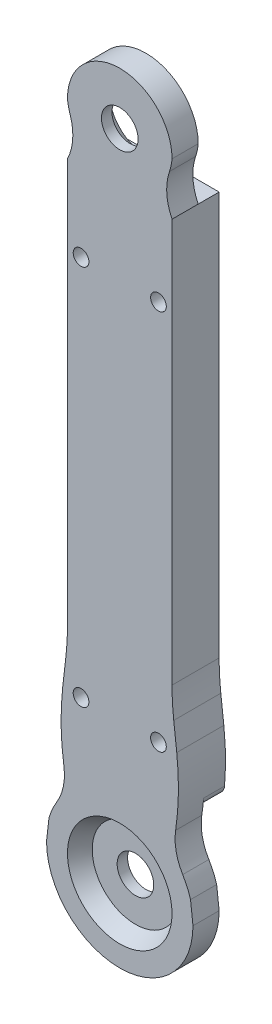
SolidWorks part; units mm, degrees
ref_plane "Front Plane" through (0, 0, 0) normal (0, 0, 1) x (1, 0, 0)
ref_plane "Top Plane" through (0, 0, 0) normal (0, 1, 0) x (1, 0, 0)
ref_plane "Right Plane" through (0, 0, 0) normal (1, 0, 0) x (0, 0, -1)
sketch "Sketch1" plane through (0, 0, 0) normal (0, 0, 1) x (1, 0, 0)
  line L1 (-14, 0) -> (-10, 35)
  line L2 (-10, 35) -> (10, 35)
  line L3 (14, 0) -> (10, 35)
  arc A0 (-14, 0) -> (13.639, 3.1587) centre (0, 0) ccw
  dimension "D1" = 28
  dimension "D3" = 35
extrude "Boss-Extrude1" add sketch "Sketch1" along normal blind 5 contours L1 A0 L3 L2 region at (0, 10.5011, 0)
sketch "Sketch2" plane through (0, 0, 5) normal (0, 0, 1) x (1, 0, 0)
  line L0 (-10, 35) -> (-10, 125) construction
  line L2 (10, 35) -> (-10, 35)
  line L3 (10, 35) -> (10, 125)
  line L4 (10, 125) -> (-10, 125)
  line L5 (-10, 35) -> (-10, 125)
  dimension "D1" = 90
extrude "Boss-Extrude2" add sketch "Sketch2" against normal blind 5
sketch "Sketch3" plane through (0, 0, 0) normal (0, 0, -1) x (-1, 0, 0)
  line L0 (-14, 0) -> (-10, 35) construction
  line L1 (-13.5314, 4.1) -> (-11.7143, 20)
  line L2 (-29.2308, 20) -> (51.5623, 20) construction
  line L3 (-29.2308, 4.1) -> (51.5623, 4.1) construction
  line L4 (-11.7143, 20) -> (-10, 10.0973)
  line L5 (0, 0) -> (0, 31.7524) construction
  line L6 (11.7143, 20) -> (10, 10.0973)
  line L7 (13.5314, 4.1) -> (11.7143, 20)
  arc A0 (-10, 10.0973) -> (-13.5314, 4.1) centre (0.1152, 0.1027) ccw
  arc A1 (10, 10.0973) -> (13.5314, 4.1) centre (-0.1152, 0.1027) cw
  dimension "D4" = 14.22
  dimension "D1" = 4.1
  dimension "D2" = 20
  dimension "D3" = 10.05
  dimension "D5" = 10
extrude "Cut-Extrude1" cut sketch "Sketch3" against normal blind 5
sketch "Sketch4" plane through (0, 0, 0) normal (0, 0, -1) x (-1, 0, 0)
  line L0 (-10.6635, 13.93) -> (10.6635, 13.93) construction
  line L1 (-10, 10.0973) -> (-11.7143, 20) construction
  line L2 (11.7143, 20) -> (10, 10.0973) construction
  line L3 (11.7143, 20) -> (10, 35) construction
  line L4 (-11.7143, 20) -> (-10, 35) construction
  line L5 (10, 125) -> (10, 35) construction
  line L6 (-10, 35) -> (-10, 125) construction
  line L7 (11.7143, 20) -> (10.6635, 13.93)
  line L8 (-10.6635, 13.93) -> (-11.7143, 20)
  line L9 (11.7143, 20) -> (10, 35)
  line L10 (-11.7143, 20) -> (-10, 35)
  line L11 (10, 115) -> (10, 35)
  line L12 (-10, 35) -> (-10, 115)
  line L13 (-10, 115) -> (10, 115)
  line L14 (-10, 125) -> (10, 125) construction
  arc A0 (-10.6635, 13.93) -> (10.6635, 13.93) centre (0, -0.0089) cw
  dimension "D2" = 17.55
  dimension "D1" = 13.93
  dimension "D3" = 10
extrude "Boss-Extrude3" add sketch "Sketch4" along normal blind 4
sketch "Sketch5" plane through (0, 0, 0) normal (0, 0, -1) x (-1, 0, 0)
  circle A0 centre (0, 0) radius 3.5
  dimension "D1" = 7
extrude "Cut-Extrude2" cut sketch "Sketch5" against normal blind 32
sketch "Sketch6" plane through (0, 0, 5) normal (0, 0, 1) x (1, 0, 0)
  circle A0 centre (0, 0) radius 10
  dimension "D1" = 20
extrude "Cut-Extrude3" cut sketch "Sketch6" against normal blind 3 draft 30
sketch "Sketch7" plane through (0, 0, 5) normal (0, 0, 1) x (1, 0, 0)
  line L0 (0, 0) -> (0, 125) construction
  line L1 (10, 125) -> (-10, 125) construction
  line L3 (-7.4, 100) -> (7.4, 100) construction
  line L4 (-7.4, 100) -> (-7.4, 27.09) construction
  line L5 (-7.4, 27.09) -> (7.4, 27.09) construction
  line L6 (7.4, 100) -> (7.4, 27.09) construction
  circle A0 centre (-7.4, 27.09) radius 1.5
  circle A1 centre (7.4, 27.09) radius 1.5
  circle A2 centre (-7.4, 100) radius 1.5
  circle A3 centre (7.4, 100) radius 1.5
  dimension "D4" = 3
  dimension "D5" = 3
  dimension "D6" = 3
  dimension "D7" = 3
  dimension "D1" = 25
  dimension "D2" = 14.8
  dimension "D3" = 72.91
extrude "Cut-Extrude4" cut sketch "Sketch7" against normal through all
sketch "Sketch8" plane through (0, 0, -4) normal (0, 0, -1) x (-1, 0, 0)
  line L0 (0, 115) -> (0, 0) construction
  line L1 (10, 115) -> (-10, 115) construction
  line L2 (3, 115) -> (-3, 115)
  line L3 (-3, 115) -> (-3, 100)
  line L4 (-3, 100) -> (-7, 91.1451)
  line L5 (-7, 91.1451) -> (-7, 41.1451)
  line L6 (-7, 66.1451) -> (10, 66.1451) construction
  line L7 (10, 35) -> (10, 115) construction
  line L8 (-3, 32.2902) -> (-7, 41.1451)
  line L9 (-3, 17.2902) -> (-3, 32.2902)
  line L10 (3, 17.2902) -> (-3, 17.2902)
  line L11 (7, 66.1451) -> (-10, 66.1451) construction
  line L12 (3, 17.2902) -> (3, 32.2902)
  line L13 (3, 32.2902) -> (7, 41.1451)
  line L14 (7, 91.1451) -> (7, 41.1451)
  line L15 (3, 100) -> (7, 91.1451)
  line L16 (3, 115) -> (3, 100)
  point P19 (0, 17.2902)
  dimension "D1" = 3
  dimension "D2" = 15
  dimension "D3" = 25
  dimension "D4" = 7
  dimension "D5" = 155.69
extrude "Cut-Extrude5" cut sketch "Sketch8" against normal blind 4
fillet "Fillet1" radius 10 8 edges at (-7, 91.1451, -2) (-3, 100, -2) (-7, 41.1451, -2) (-3, 32.2902, -2) (3, 32.2902, -2) (7, 41.1451, -2) (7, 91.1451, -2) (3, 100, -2)
fillet "Fillet2" radius 2 4 edges at (-2.957, 17.2902, -2) (3, 17.2902, -2) (-3, 115, -2) (3, 115, -2)
fillet "Fillet3" radius 50 4 edges at (10, 35, 0.5) (-10, 35, 0.5) (-11.7143, 20, 0.5) (11.7143, 20, 0.5)
fillet "Fillet4" radius 10 2 edges at (-10, 10.0973, 2.5) (10, 10.0973, 2.5)
fillet "Fillet5" radius 2 2 edges at (-10.6566, 13.9353, -2) (10.6566, 13.9353, -2)
sketch "Sketch9" plane through (0, 0, 0) normal (0, 0, -1) x (-1, 0, 0)
  line L0 (-10, 125) -> (10, 125) construction
  circle A0 centre (0, 125) radius 10
  dimension "D1" = 20
extrude "Boss-Extrude4" add sketch "Sketch9" against normal up to surface (5 mm away) up to face at (8.9, 27.09, 5)
sketch "Sketch10" plane through (0, 0, 0) normal (0, 0, -1) x (-1, 0, 0)
  line L0 (-10, 115) -> (-10, 125) construction
  line L1 (-10, 115) -> (-10, 125)
sketch "Sketch11" plane through (0, 0, 0) normal (0, 0, -1) x (-1, 0, 0)
  line L0 (-10, 115) -> (-10, 125) construction
  line L5 (-10, 115) -> (-10, 125)
  line L6 (-10, 115) -> (-7.5, 119.21)
  line L7 (0, 135) -> (0, 108.1715) construction
  line L8 (10, 115) -> (7.5, 119.21)
  line L9 (10, 115) -> (10, 125)
  arc A2 (-10, 125) -> (-7.5, 119.21) centre (-0.0376, 125.8668) ccw
  arc A3 (10, 125) -> (-10, 125) centre (0, 125) ccw construction
  arc A4 (10, 125) -> (7.5, 119.21) centre (0.0376, 125.8668) cw
  dimension "D1" = 4.21
  dimension "D2" = 10
  dimension "D3" = 7.5
extrude "Cut-Extrude6" cut sketch "Sketch11" against normal through all
fillet "Fillet6" radius 10 2 edges at (7.5, 119.21, 2.5) (-7.5, 119.21, 2.5)
sketch "Sketch12" plane through (0, 0, 0) normal (0, 0, -1) x (-1, 0, 0)
  circle A0 centre (0, 125) radius 7
  dimension "D1" = 14
extrude "Cut-Extrude7" cut sketch "Sketch12" against normal blind 3 draft 30
sketch "Sketch13" plane through (0, 0, 3) normal (0, 0, -1) x (-1, 0, 0)
  circle A0 centre (0, 125) radius 3.5
  dimension "D1" = 7
extrude "Cut-Extrude8" cut sketch "Sketch13" against normal through all
